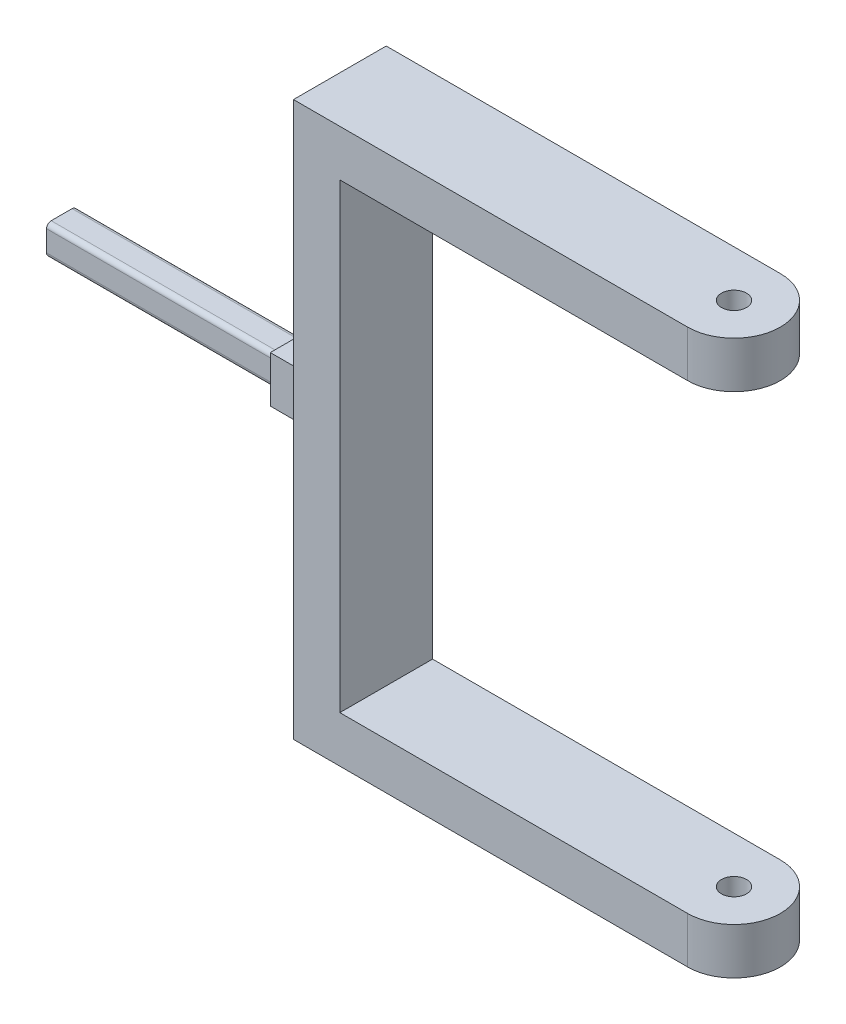
SolidWorks part; units mm, degrees
ref_plane "前视基准面" through (0, 0, 0) normal (0, 0, 1) x (1, 0, 0)
ref_plane "上视基准面" through (0, 0, 0) normal (0, 1, 0) x (1, 0, 0)
ref_plane "右视基准面" through (0, 0, 0) normal (1, 0, 0) x (0, 0, -1)
other "Configuration Table"
sketch "草图1" plane through (0, 0, 0) normal (0, 0, 1) x (1, 0, 0)
  line L0 (0, 49.75) -> (0, -49.75)
  line L1 (0, 49.75) -> (85, 49.75)
  line L2 (85, 49.75) -> (85, 59.75)
  line L3 (85, 59.75) -> (-10, 59.75)
  line L4 (-10, 59.75) -> (-10, -59.75)
  line L5 (-10, -59.75) -> (85, -59.75)
  line L6 (85, -59.75) -> (85, -49.75)
  line L7 (85, -49.75) -> (0, -49.75)
  point P4 (0, 0)
  dimension "D1" = 99.5
  dimension "D2" = 85
  dimension "D3" = 10
  dimension "D4" = 10
  dimension "D5" = 10
extrude "凸台-拉伸1" add sketch "草图1" along normal blind 20
sketch "草图3" plane through (-10, 0, 0) normal (-1, 0, 0) x (0, 0, 1)
  line L0 (0, 59.75) -> (20, -59.75) construction
  line L1 (0, -59.75) -> (20, 59.75) construction
  line L2 (6.75, 3.25) -> (13.25, 3.25)
  line L3 (5, 5) -> (15, 5)
  line L4 (0, 59.75) -> (0, -59.75)
  line L5 (0, -59.75) -> (20, -59.75)
  line L6 (20, -59.75) -> (20, 59.75)
  line L7 (20, 59.75) -> (0, 59.75)
  line L8 (0, 59.75) -> (0, -59.75)
  line L9 (0, -59.75) -> (20, -59.75)
  line L10 (20, -59.75) -> (20, 59.75)
  line L11 (20, 59.75) -> (0, 59.75)
  line L12 (5, 5) -> (5, -5)
  line L13 (5, -5) -> (15, -5)
  line L14 (15, 5) -> (15, -5)
  line L15 (5, 5) -> (15, -5) construction
  line L16 (5, -5) -> (15, 5) construction
  line L17 (13.25, 3.25) -> (13.25, -3.25)
  line L18 (6.75, -3.25) -> (13.25, -3.25)
  line L19 (6.75, 3.25) -> (6.75, -3.25)
  point P4 (10, 0)
  dimension "D2" = 10
  dimension "D3" = 1.75
  dimension "D1" = 0
extrude "凸台-拉伸2" add sketch "草图3" along normal blind 10 contours L14 L3 L12 L13 L19 L2 L17 L18 | L2 L19 L18 L17 region at (-10, 0, 10) region at (-10, 4.8586, 10)
extrude "凸台-拉伸3" add sketch "草图3<3>" along normal blind 50 from surface contours L2 L19 L18 L17 region at (-10, 0, 10) starting at face at (-20, 0, 10)
sketch "草图3<3>" plane through (-10, 0, 0) normal (-1, 0, 0) x (0, 0, 1) same geometry as "草图3"
sketch "草图4" plane through (85, 0, 0) normal (1, 0, 0) x (0, 0, -1)
  line L0 (0, -59.75) -> (0, -49.75) construction
  line L1 (0, -49.75) -> (-20, -49.75) construction
  line L2 (-20, -49.75) -> (-20, -59.75) construction
  line L3 (-20, -59.75) -> (0, -59.75) construction
  line L4 (0, 49.75) -> (0, 59.75) construction
  line L5 (0, 59.75) -> (-20, 59.75) construction
  line L6 (-20, 59.75) -> (-20, 49.75) construction
  line L7 (-20, 49.75) -> (0, 49.75) construction
  line L8 (0, -59.75) -> (0, -49.75)
  line L9 (0, -49.75) -> (-20, -49.75)
  line L10 (-20, -49.75) -> (-20, -59.75)
  line L11 (-20, -59.75) -> (0, -59.75)
  line L12 (0, 49.75) -> (0, 59.75)
  line L13 (0, 59.75) -> (-20, 59.75)
  line L14 (-20, 59.75) -> (-20, 49.75)
  line L15 (-20, 49.75) -> (0, 49.75)
ref_plane "基准面1" through (0, 0, 10) normal (0, 0, 1) x (1, 0, 0)
ref_axis "基准轴1" through (-20, -5, 10) along (0, 1, 0)
sketch "草图5" plane through (0, 59.75, 0) normal (0, 1, 0) x (1, 0, 0)
  line L0 (85, -10) -> (-10, -10) construction
  line L1 (85, -20) -> (85, 0) construction
  line L2 (-5.5, -10) -> (5.5, -10) construction
  line L3 (-10, -5) -> (-10, -15) construction
  line L4 (85, 0) -> (-10, 0) construction
  circle A0 centre (75, -10) radius 10
  circle A1 centre (75, -10) radius 2.7
  line M1 (85, 0) -> (-10, 0)
  line M3 (-10, -20) -> (85, -20)
  line M4 (85, -20) -> (85, 0)
  dimension "D1" = 5.4
extrude "切除-拉伸1" cut sketch "草图5" against normal through all contours A1 L0 | L0 A1 | A0 M3 M4 | A0 M4 M1 region at (82.7663, 59.75, 17.7663) region at (82.7663, 59.75, 2.2337) region at (75, 59.75, 11.1459) region at (75, 59.75, 8.8541)
fillet "圆角1" radius 1 4 edges at (-45, -3.25, 13.25) (-45, 3.25, 13.25) (-45, -3.25, 6.75) (-45, 3.25, 6.75)
